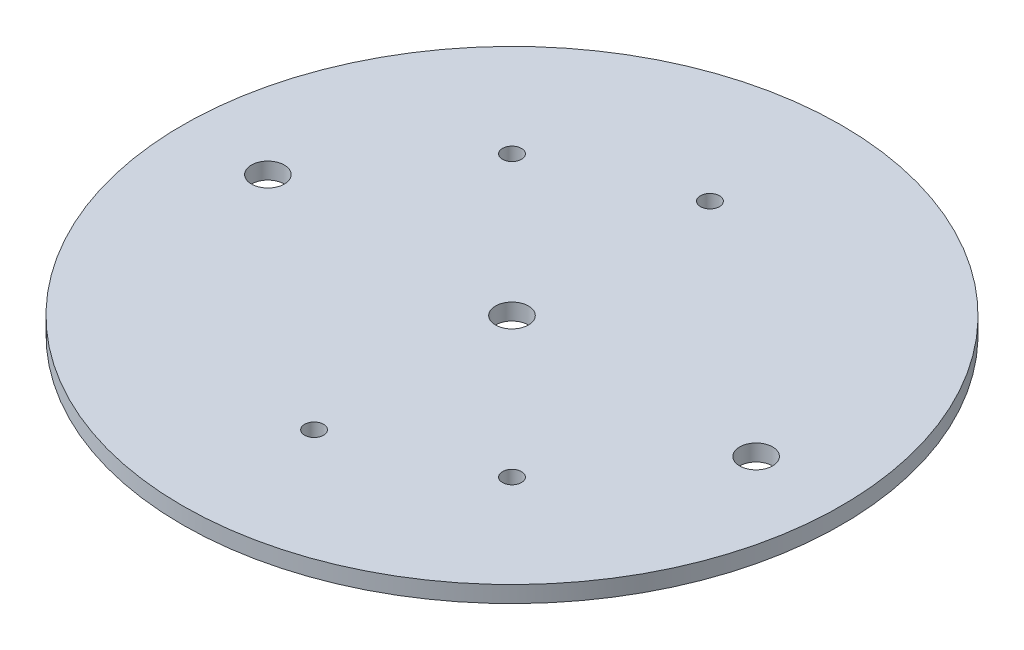
SolidWorks part; units mm, degrees
ref_plane "Front Plane" through (0, 0, 0) normal (0, 0, 1) x (1, 0, 0)
ref_plane "Top Plane" through (0, 0, 0) normal (0, 1, 0) x (1, 0, 0)
ref_plane "Right Plane" through (0, 0, 0) normal (1, 0, 0) x (0, 0, -1)
sketch "Sketch2" plane through (0, 0, 0) normal (0, 1, 0) x (1, 0, 0)
  line L0 (-46.99, 0) -> (46.99, 0) construction
  line L1 (0, -38.1) -> (0, 38.1) construction
  line L2 (-26.9408, 26.9408) -> (26.9408, -26.9408) construction
  circle A0 centre (0, 0) radius 63.4365
  circle A1 centre (-46.99, 0) radius 3.175
  circle A2 centre (46.99, 0) radius 3.175
  circle A3 centre (0, 0) radius 3.175
  circle A4 centre (0, 38.1) radius 1.8288
  circle A5 centre (0, -38.1) radius 1.8288
  circle A8 centre (-26.9408, 26.9408) radius 1.8288
  circle A9 centre (26.9408, -26.9408) radius 1.8288
  point P6 (0, 0)
  point P12 (0, 0)
  point P17 (0, 0)
  point P18 (0, 0)
  dimension "D1" = 126.873
  dimension "D3" = 6.35
  dimension "D4" = 6.35
  dimension "D5" = 3.6576
  dimension "D6" = 76.2
  dimension "D8" = 45
  dimension "D7" = 76.2
  dimension "D2" = 93.98
extrude "Boss-Extrude1" add sketch "Sketch2" along normal blind 3.175
